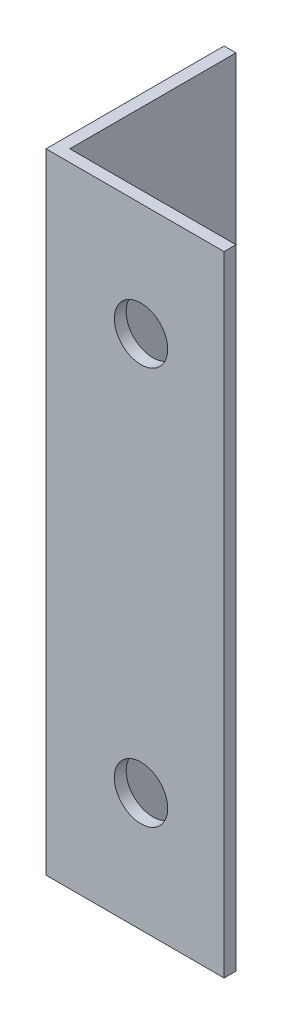
SolidWorks part; units mm, degrees
material "1060 Сплав"
ref_plane "Спереди" through (0, 0, 0) normal (0, 0, 1) x (1, 0, 0)
ref_plane "Сверху" through (0, 0, 0) normal (0, 1, 0) x (1, 0, 0)
ref_plane "Справа" through (0, 0, 0) normal (1, 0, 0) x (0, 0, -1)
sketch "Эскиз1" plane through (0, 0, 0) normal (0, 1, 0) x (1, 0, 0)
  line L0 (0, 0) -> (0, 15)
  line L1 (0, 15) -> (1, 15)
  line L2 (1, 15) -> (1, 1)
  line L3 (1, 1) -> (15, 1)
  line L4 (15, 1) -> (15, 0)
  line L5 (15, 0) -> (0, 0)
  dimension "D1" = 1
  dimension "D2" = 15
extrude "Бобышка-Вытянуть1" add sketch "Эскиз1" along normal blind 53
sketch "Эскиз2" plane through (0, 0, -1) normal (0, 0, -1) x (-1, 0, 0)
  line L0 (-8, 0) -> (-8, 53) construction
  line L1 (-15, 0) -> (-1, 0) construction
  line L2 (-15, 53) -> (-1, 53) construction
  circle A0 centre (-8, 10) radius 2.25
  circle A1 centre (-8, 43.5) radius 2.25
  dimension "D1" = 4.5
  dimension "D2" = 4.5
  dimension "D3" = 10
  dimension "D4" = 9.5
extrude "Вырез-Вытянуть1" cut sketch "Эскиз2" against normal through all
sketch "Эскиз4" plane through (0, 0, 0) normal (-1, 0, 0) x (0, 0, 1)
  line L0 (-7.5, 53) -> (-7.5, 0) construction
  line L1 (-15, 53) -> (0, 53) construction
  line L2 (-15, 0) -> (0, 0) construction
